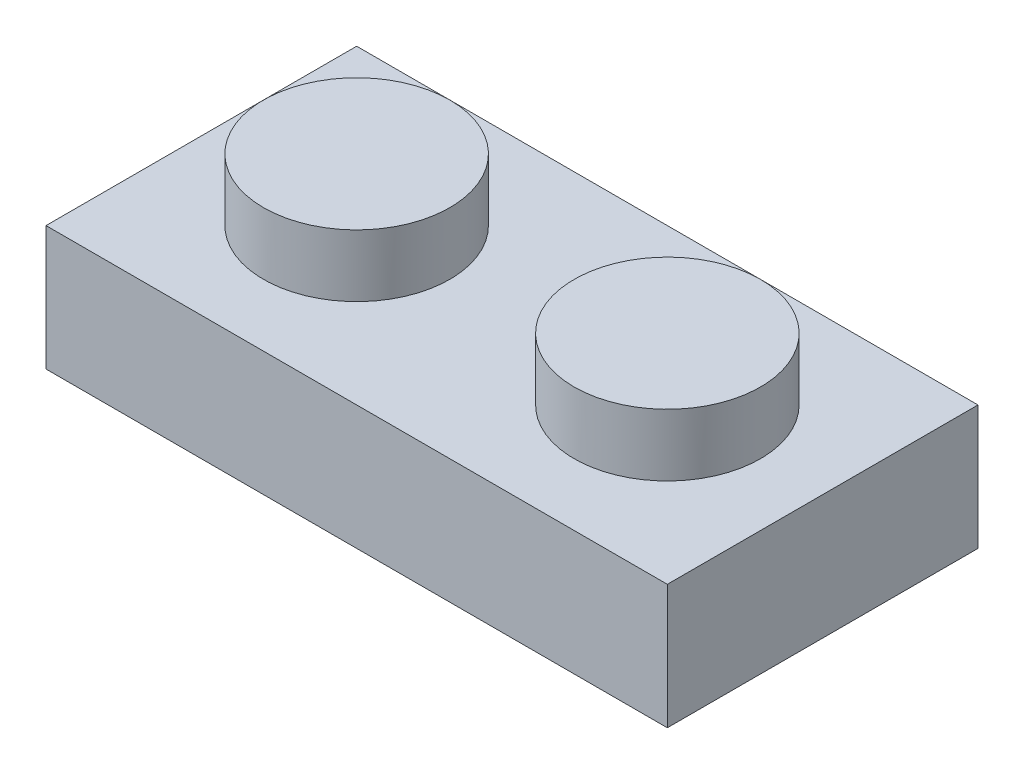
SolidWorks part; units mm, degrees
ref_plane "Front Plane" through (0, 0, 0) normal (0, 0, 1) x (1, 0, 0)
ref_plane "Top Plane" through (0, 0, 0) normal (0, 1, 0) x (1, 0, 0)
ref_plane "Right Plane" through (0, 0, 0) normal (1, 0, 0) x (0, 0, -1)
sketch "Sketch1" plane through (0, 0, 0) normal (0, 1, 0) x (1, 0, 0)
  line L1 (-5, 2.5) -> (5, 2.5)
  line L2 (-5, 2.5) -> (-5, -2.5)
  line L3 (-5, -2.5) -> (5, -2.5)
  line L4 (5, 2.5) -> (5, -2.5)
  line L5 (-5, 2.5) -> (5, -2.5) construction
  line L6 (-5, -2.5) -> (5, 2.5) construction
  line L7 (-4, -1.5) -> (4, -1.5)
  line L8 (-4, -1.5) -> (-4, 1.5)
  line L9 (-4, 1.5) -> (4, 1.5)
  line L10 (4, -1.5) -> (4, 1.5)
  line L11 (-4, -1.5) -> (4, 1.5) construction
  line L12 (-4, 1.5) -> (4, -1.5) construction
  circle A0 centre (-2.5, 0) radius 1.5
  circle A1 centre (2.5, 0) radius 1.5
  circle A2 centre (-2.5, 0) radius 0.75
  circle A3 centre (2.5, 0) radius 0.75
  circle A4 centre (0, 0) radius 1
  point P0 (0, 0)
  point P6 (0, 0)
  dimension "D5" = 1.5
  dimension "D1" = 5
  dimension "D2" = 10
  dimension "D3" = 1
  dimension "D4" = 1
  dimension "D6" = 2
extrude "Boss-Extrude1" add sketch "Sketch1" along normal blind 2 contours A0 A2 | A2 | A3 | A1 A3 region at (-3.5307, 0, 1.0307) region at (1.4693, 0, 1.0307) region at (-2.5, 0, 0) region at (2.5, 0, 0)
extrude "Boss-Extrude2" add sketch "Sketch1<3>" along normal blind 1 contours L2 L3 L4 L1
sketch "Sketch1<3>" plane through (0, 0, 0) normal (0, 1, 0) x (1, 0, 0) same geometry as "Sketch1"
extrude "Cut-Extrude1" cut sketch "Sketch1<4>" along normal blind 1 contours A2 | A3 region at (-2.5, 0, 0) region at (2.5, 0, 0)
sketch "Sketch1<4>" plane through (0, 0, 0) normal (0, 1, 0) x (1, 0, 0) same geometry as "Sketch1"
extrude "Boss-Extrude3" add sketch "Sketch1<5>" against normal blind 1 contours A4 | L4 L1 L2 L3 L10 L7 L8 L9 region at (0, 0, -2.3882) region at (0, 0, 0)
sketch "Sketch1<5>" plane through (0, 0, 0) normal (0, 1, 0) x (1, 0, 0) same geometry as "Sketch1"
